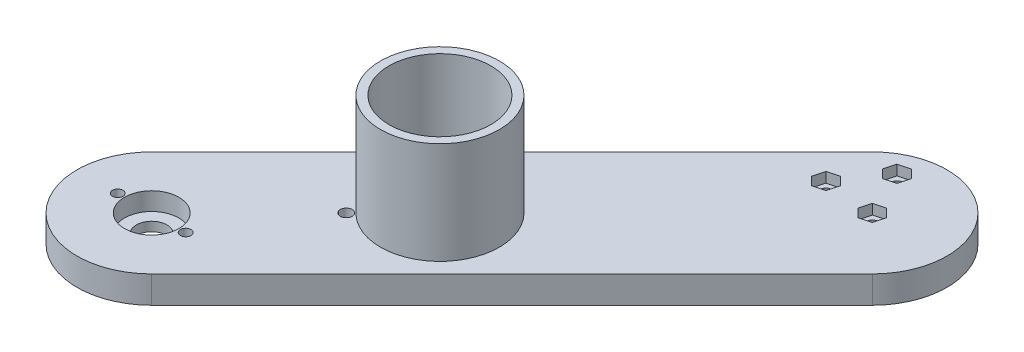
SolidWorks part; units mm, degrees
ref_plane "Front Plane" through (0, 0, 0) normal (0, 0, 1) x (1, 0, 0)
ref_plane "Top Plane" through (0, 0, 0) normal (0, 1, 0) x (1, 0, 0)
ref_plane "Right Plane" through (0, 0, 0) normal (1, 0, 0) x (0, 0, -1)
sketch "Sketch1" plane through (0, 0, 0) normal (0, 1, 0) x (1, 0, 0)
  line L0 (0, 0) -> (106.066, 106.066) construction
  line L25 (-15.5563, 15.5563) -> (90.5097, 121.6224)
  line L26 (15.5563, -15.5563) -> (121.6224, 90.5097)
  line L27 (106.066, 106.066) -> (-3.1733, 182.5562) construction
  line L28 (97.4624, 93.7787) -> (-11.777, 170.269)
  line L29 (114.6697, 118.3533) -> (5.4303, 194.8435)
  line L30 (99.7189, 119.6662) -> (91.1152, 107.3789) construction
  line L31 (106.9626, 109.4121) -> (103.6165, 108.5155)
  line L32 (103.6165, 108.5155) -> (102.72, 105.1694)
  line L33 (102.72, 105.1694) -> (105.1694, 102.72)
  line L34 (105.1694, 102.72) -> (108.5155, 103.6165)
  line L35 (108.5155, 103.6165) -> (109.4121, 106.9626)
  line L36 (109.4121, 106.9626) -> (106.9626, 109.4121)
  line L37 (97.2329, 93.4511) -> (-12.0064, 169.9413)
  line L38 (90.2186, 104.0328) -> (93.5647, 104.9294)
  line L39 (93.5647, 104.9294) -> (94.4613, 108.2754)
  line L40 (94.4613, 108.2754) -> (92.0118, 110.7249)
  line L41 (92.0118, 110.7249) -> (88.6657, 109.8284)
  line L42 (88.6657, 109.8284) -> (87.7692, 106.4823)
  line L43 (87.7692, 106.4823) -> (90.2186, 104.0328)
  line L44 (100.6154, 123.0122) -> (97.2694, 122.1156)
  line L45 (97.2694, 122.1156) -> (96.3728, 118.7696)
  line L46 (96.3728, 118.7696) -> (98.8223, 116.3201)
  line L47 (98.8223, 116.3201) -> (102.1684, 117.2167)
  line L48 (102.1684, 117.2167) -> (103.0649, 120.5627)
  line L49 (103.0649, 120.5627) -> (100.6154, 123.0122)
  line L66 (114.8991, 118.681) -> (5.6597, 195.1712)
  arc A12 (-15.5563, 15.5563) -> (15.5563, -15.5563) centre (0, 0) ccw
  arc A13 (121.6224, 90.5097) -> (90.5097, 121.6224) centre (106.066, 106.066) ccw
  arc A14 (97.4624, 93.7787) -> (114.6697, 118.3533) centre (106.066, 106.066) ccw
  arc A15 (5.4303, 194.8435) -> (-11.777, 170.269) centre (-3.1733, 182.5562) ccw
  circle A16 centre (106.066, 106.066) radius 1.7
  circle A17 centre (106.066, 106.066) radius 3 construction
  circle A18 centre (99.7189, 119.6662) radius 1.7
  circle A19 centre (91.1152, 107.3789) radius 1.7
  circle A20 centre (91.1152, 107.3789) radius 3 construction
  circle A21 centre (99.7189, 119.6662) radius 3 construction
  arc A22 (5.6597, 195.1712) -> (-12.0064, 169.9413) centre (-3.1733, 182.5562) ccw
  arc A23 (97.2329, 93.4511) -> (114.8991, 118.681) centre (106.066, 106.066) ccw
  point P1 (0, 0)
  point P2 (0, 0)
  point P3 (1.899, -1.7321)
  point P4 (0, 0)
  point P14 (53.033, 53.033)
  point P50 (51.4463, 144.3111)
  point P66 (95.417, 113.5225)
  point P98 (0, 0)
  point P99 (0, 0)
  dimension "D17" = 15
  dimension "D18" = 3.4
  dimension "D19" = 6
  dimension "D20" = 3.4
  dimension "D22" = 3.4
  dimension "D23" = 6
  dimension "D24" = 6
  dimension "D14" = 45
  dimension "D15" = 150
  dimension "D16" = 80
  dimension "D21" = 15
  dimension "D25" = 13
  dimension "D26" = 0.4
extrude "Boss-Extrude1" add sketch "Sketch1" along normal blind 8 contours L26 A13 L25 A12
sketch "Sketch4" plane through (0, 0, 0) normal (0, 1, 0) x (1, 0, 0)
  line L0 (-10, 0) -> (10, 0) construction
  line L7 (0, 0) -> (106.066, 106.066) construction
  line L48 (42.4264, 50.4264) -> (42.4264, 34.4264) construction
  line L49 (42.4264, 42.4264) -> (0, 0) construction
  circle A0 centre (42.4264, 42.4264) radius 15
  circle A18 centre (42.4264, 50.4264) radius 1.1
  circle A19 centre (42.4264, 34.4264) radius 1.1
  circle A21 centre (42.4264, 42.4264) radius 5.75
  circle A22 centre (0, 0) radius 8
  circle A23 centre (0, 0) radius 4.5
  circle A24 centre (-10, 0) radius 1.55
  circle A25 centre (10, 0) radius 1.55
  circle A26 centre (0, 0) radius 32.5 construction
  circle A27 centre (42.4264, 42.4264) radius 17.5
  circle A28 centre (28.6378, 28.6378) radius 1.75
  point P59 (0, 0)
  dimension "D3" = 60
  dimension "D4" = 2.2
  dimension "D5" = 16
  dimension "D6" = 11.5
  dimension "D7" = 2.2
  dimension "D10" = 40.5
  dimension "D11" = 3.5
  dimension "D8" = 30
  dimension "D9" = 35
  dimension "D18" = 9
  dimension "D19" = 16
  dimension "D20" = 3.1
  dimension "D21" = 3.1
  dimension "D23" = 65
  dimension "D22" = 20
extrude "Boss-Extrude3" add sketch "Sketch4" along normal blind 30 from surface contours A27 A0 starting at face at (53.033, 8, -53.033)
extrude "Cut-Extrude9" cut sketch "Sketch4<5>" along normal through all both and the other way through all contours A23 | A21 | A18 | A19 | A28 region at (42.4264, 0, -50.4264) region at (42.4264, 0, -34.4264) region at (42.4264, 0, -42.4264) region at (0, 0, 0) region at (28.6378, 0, -28.6378)
sketch "Sketch4<5>" plane through (0, 0, 0) normal (0, 1, 0) x (1, 0, 0) same geometry as "Sketch4"
extrude "Cut-Extrude5" cut sketch "Sketch1<8>" against normal blind 3 from surface contours L48 L49 L44 L45 L46 L47 A18 | L42 L43 L38 L39 L40 L41 A19 | L35 L36 L31 L32 L33 L34 A16 region at (108.1204, 0, -108.1204) region at (89.0608, 0, -105.3245) region at (101.7733, 0, -121.7206) starting at face at (0, 8, 4.5)
sketch "Sketch1<8>" plane through (0, 0, 0) normal (0, 1, 0) x (1, 0, 0) same geometry as "Sketch1"
extrude "Cut-Extrude6" cut sketch "Sketch1<9>" along normal blind 3 from surface contours L66 A22 L37 A23 starting at face at (0, 0, 4.5)
sketch "Sketch1<9>" plane through (0, 0, 0) normal (0, 1, 0) x (1, 0, 0) same geometry as "Sketch1"
extrude "Cut-Extrude11" cut sketch "Sketch4<7>" against normal blind 5.3 from surface contours A22 A23 | A25 | A24 region at (-7.7737, 0, 0) region at (-10, 0, 0) region at (10, 0, 0) starting at face at (91.1152, 8, -107.3789)
sketch "Sketch4<7>" plane through (0, 0, 0) normal (0, 1, 0) x (1, 0, 0) same geometry as "Sketch4"
extrude "Cut-Extrude13" cut sketch "Sketch1<10>" along normal through all both and the other way through all contours A18 | A19 | A16 region at (106.066, 0, -106.066) region at (99.7189, 0, -119.6662) region at (91.1152, 0, -107.3789)
sketch "Sketch1<10>" plane through (0, 0, 0) normal (0, 1, 0) x (1, 0, 0) same geometry as "Sketch1"
extrude "Cut-Extrude14" cut sketch "Sketch4<8>" against normal blind 6 from surface contours A0 starting at face at (42.4264, 8, -49.3264)
sketch "Sketch4<8>" plane through (0, 0, 0) normal (0, 1, 0) x (1, 0, 0) same geometry as "Sketch4"
